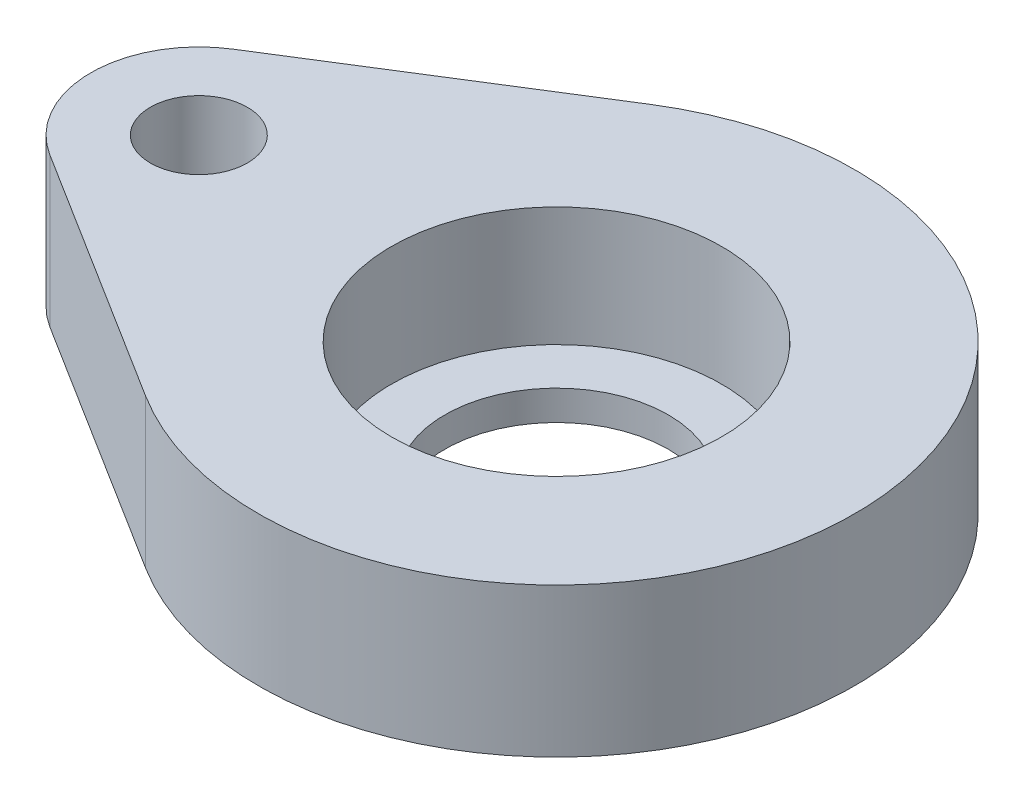
SolidWorks part; units mm, degrees
ref_plane "Ebene vorne" through (0, 0, 0) normal (0, 0, 1) x (1, 0, 0)
ref_plane "Ebene oben" through (0, 0, 0) normal (0, 1, 0) x (1, 0, 0)
ref_plane "Ebene rechts" through (0, 0, 0) normal (1, 0, 0) x (0, 0, -1)
sketch "Skizze1" plane through (0, 0, 0) normal (0, 1, 0) x (1, 0, 0)
  line L0 (0, 0) -> (24, 0) construction
  line L1 (-3.8516, -6.1423) -> (13.375, -16.9443)
  line L2 (-3.8516, 6.1423) -> (13.375, 16.9443)
  arc A0 (-3.8516, 6.1423) -> (-3.8516, -6.1423) centre (0, 0) ccw
  arc A1 (13.375, 16.9443) -> (13.375, -16.9443) centre (24, 0) cw
  dimension "D2" = 7.25
  dimension "D3" = 20
  dimension "D1" = 24
extrude "Aufsatz-Linear austragen1" add sketch "Skizze1" along normal blind 10
sketch "Skizze2" plane through (0, 10, 0) normal (0, 1, 0) x (1, 0, 0)
  line L0 (0, 0) -> (24, 0) construction
  circle A0 centre (0, 0) radius 3.25
  circle A1 centre (24, 0) radius 11.075
  dimension "D1" = 6.5
  dimension "D3" = 22.15
  dimension "D2" = 24
extrude "Schnitt-Linear austragen1" cut sketch "Skizze2" against normal blind 8
sketch "Skizze3" plane through (0, 2, 0) normal (0, 1, 0) x (1, 0, 0)
  circle A0 centre (24, 0) radius 7.5
  circle A1 centre (0, 0) radius 1.5
  dimension "D1" = 3
  dimension "D2" = 15
extrude "Schnitt-Linear austragen2" cut sketch "Skizze3" against normal up to surface (2 mm away) up to face at (11.5684, 0, 0)
